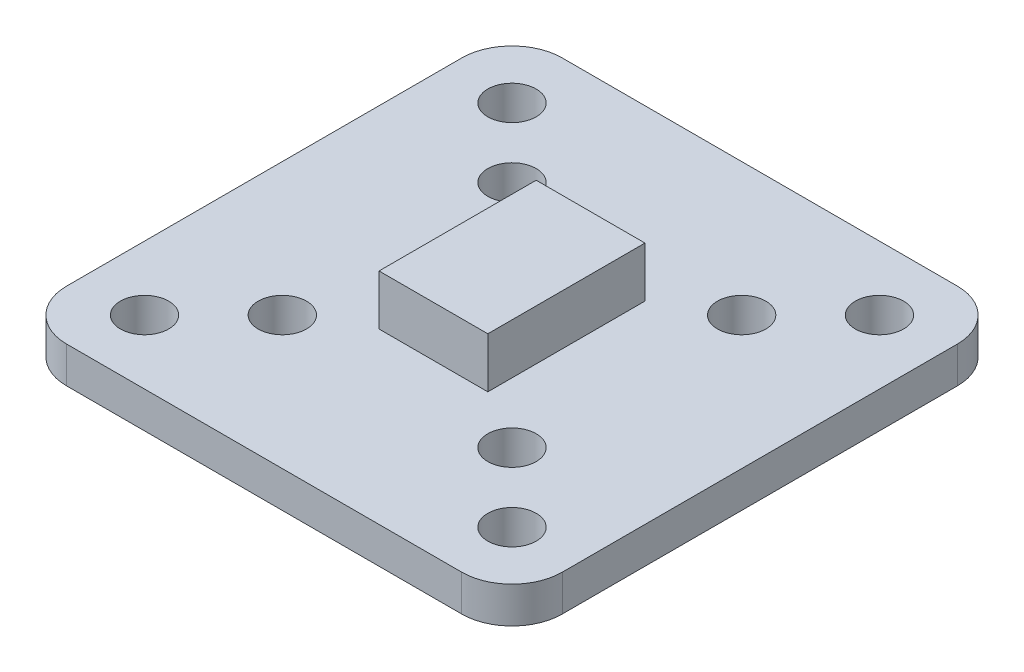
SolidWorks part; units mm, degrees
ref_plane "Front Plane" through (0, 0, 0) normal (0, 0, 1) x (1, 0, 0)
ref_plane "Top Plane" through (0, 0, 0) normal (0, 1, 0) x (1, 0, 0)
ref_plane "Right Plane" through (0, 0, 0) normal (1, 0, 0) x (0, 0, -1)
sketch "Sketch1" plane through (0, 0, 0) normal (0, 1, 0) x (1, 0, 0)
  line L0 (-16.2719, 0) -> (16.2719, 0) construction
  line L1 (12.9699, -16.2719) -> (-12.9699, -16.2719)
  line L2 (16.2719, -12.9699) -> (16.2719, 12.9699)
  line L3 (12.9699, 16.2719) -> (-12.9699, 16.2719)
  line L4 (-16.2719, -12.9699) -> (-16.2719, 12.9699)
  line L5 (16.2719, -16.2719) -> (-16.2719, 16.2719) construction
  line L6 (16.2719, 16.2719) -> (-16.2719, -16.2719) construction
  line L7 (3.5719, -5.1594) -> (-3.5719, -5.1594)
  line L8 (3.5719, -5.1594) -> (3.5719, 5.1594)
  line L9 (3.5719, 5.1594) -> (-3.5719, 5.1594)
  line L10 (-3.5719, -5.1594) -> (-3.5719, 5.1594)
  line L11 (3.5719, -5.1594) -> (-3.5719, 5.1594) construction
  line L12 (3.5719, 5.1594) -> (-3.5719, -5.1594) construction
  line L13 (-5.5562, 5.5562) -> (5.5562, 5.5562)
  line L14 (-5.5562, 5.5562) -> (-5.5562, -5.5562)
  line L15 (-5.5562, -5.5562) -> (5.5562, -5.5562)
  line L16 (5.5562, 5.5562) -> (5.5562, -5.5562)
  line L17 (-5.5562, 5.5562) -> (5.5562, -5.5562) construction
  line L18 (-5.5562, -5.5562) -> (5.5562, 5.5562) construction
  circle A0 centre (12.065, 12.065) radius 1.5875
  circle A1 centre (7.5406, 7.5406) radius 1.5875
  circle A2 centre (-7.5406, -7.5406) radius 1.5875
  circle A3 centre (-12.065, -12.065) radius 1.5875
  circle A4 centre (-12.065, 12.065) radius 1.5875
  circle A5 centre (-7.5406, 7.5406) radius 1.5875
  circle A6 centre (7.5406, -7.5406) radius 1.5875
  circle A7 centre (12.065, -12.065) radius 1.5875
  arc A8 (16.2719, -12.9699) -> (12.9699, -16.2719) centre (12.9699, -12.9699) cw
  arc A9 (-12.9699, -16.2719) -> (-16.2719, -12.9699) centre (-12.9699, -12.9699) cw
  arc A10 (16.2719, 12.9699) -> (12.9699, 16.2719) centre (12.9699, 12.9699) ccw
  arc A11 (-12.9699, 16.2719) -> (-16.2719, 12.9699) centre (-12.9699, 12.9699) ccw
  point P0 (0, 0)
  point P10 (0, 0)
  point P15 (0, 0)
  dimension "D3" = 4.2069
  dimension "D4" = 3.175
  dimension "D5" = 3.175
  dimension "D6" = 8.7312
  dimension "D9" = 3.302
  dimension "D1" = 32.5437
  dimension "D2" = 32.5437
  dimension "D7" = 10.3187
  dimension "D8" = 7.1437
extrude "Boss-Extrude1" add sketch "Sketch1" against normal blind 2.3813 contours L4 A11 L3 A10 L2 A8 L1 A9
extrude "Boss-Extrude2" add sketch "Sketch1<4>" along normal blind 3.302 contours L10 L9 L8 L7
sketch "Sketch1<4>" plane through (0, 0, 0) normal (0, 1, 0) x (1, 0, 0) same geometry as "Sketch1"
extrude "Cut-Extrude1" cut sketch "Sketch1<5>" against normal through all contours A4 | A2 | A6 | A7 | A0 | A5 | A3 | A1 region at (12.065, 0, -12.065) region at (-7.5406, 0, 7.5406) region at (-12.065, 0, -12.065) region at (7.5406, 0, 7.5406) region at (12.065, 0, 12.065)
sketch "Sketch1<5>" plane through (0, 0, 0) normal (0, 1, 0) x (1, 0, 0) same geometry as "Sketch1"
